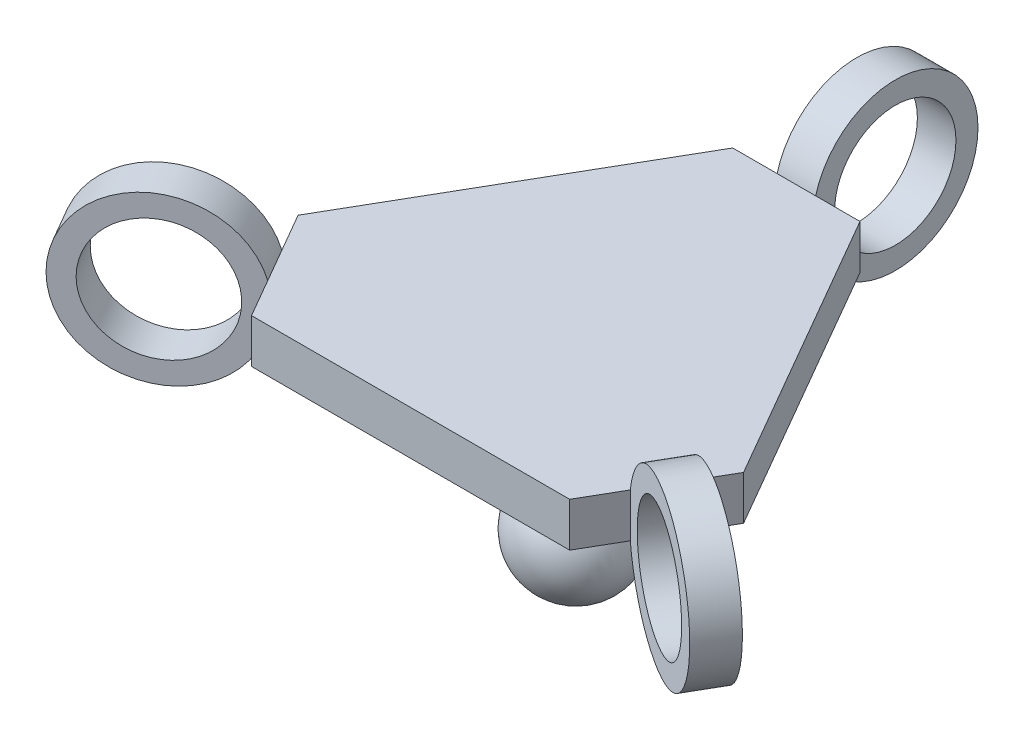
SolidWorks part; units mm, degrees
ref_plane "Front Plane" through (0, 0, 0) normal (0, 0, 1) x (1, 0, 0)
ref_plane "Top Plane" through (0, 0, 0) normal (0, 1, 0) x (1, 0, 0)
ref_plane "Right Plane" through (0, 0, 0) normal (1, 0, 0) x (0, 0, -1)
sketch "Sketch1" plane through (0, 0, 0) normal (0, 1, 0) x (1, 0, 0)
  line L0 (0, 40) -> (0, -30) construction
  line L1 (-11.547, 40) -> (-40.4145, -10)
  line L2 (-28.8675, -30) -> (28.8675, -30)
  line L3 (40.4145, -10) -> (11.547, 40)
  line L4 (11.547, 40) -> (-11.547, 40)
  line L5 (-40.4145, -10) -> (-28.8675, -30)
  line L6 (28.8675, -30) -> (40.4145, -10)
  circle A0 centre (0, 0) radius 30 construction
  circle A1 centre (0, 0) radius 40 construction
  dimension "D2" = 40
  dimension "D1" = 30
  dimension "D3" = 50
extrude "Boss-Extrude1" add sketch "Sketch1" along normal blind 8 contours L4 L1 L5 L2 L6 L3
sketch "Sketch2" plane through (0, 8, 0) normal (0, 1, 0) x (1, 0, 0)
  line L0 (0, 40) -> (0, -30) construction
  line L1 (11.547, 40) -> (-11.547, 40) construction
  line L2 (-28.8675, -30) -> (28.8675, -30) construction
  circle A0 centre (0, 0) radius 5
  dimension "D1" = 10
extrude "Cut-Extrude1" cut sketch "Sketch2" against normal blind 107
sketch "Sketch3" plane through (0, 0, 0) normal (1, 0, 0) x (0, 0, -1)
  line L0 (-34.0107, 3.4198) -> (36.0547, 3.8848) construction
  circle A0 centre (54.4549, 4.0069) radius 15
  dimension "D1" = 30
extrude "Boss-Extrude2" add sketch "Sketch3" along normal blind 3.5 and the other way blind 3.5
sketch "Sketch4" plane through (3.5, 0, 0) normal (1, 0, 0) x (0, 0, -1)
  circle A0 centre (54.4549, 4.0069) radius 11
  dimension "D1" = 22
extrude "Cut-Extrude2" cut sketch "Sketch4" against normal blind 19.5
pattern_circular "CirPattern1" count 3 over 360 about axis through (0, -99, 0) along (0, 1, 0) of bodies 104
sketch "Sketch6" plane through (0, 8, 0) normal (0, 1, 0) x (1, 0, 0)
  circle A0 centre (0, 0) radius 5
extrude "Boss-Extrude3" add sketch "Sketch6" against normal blind 34
sketch "Sketch8" plane through (0, -26, 0) normal (0, -1, 0) x (-1, 0, 0)
  line L0 (0, 0) -> (0, 50000) construction
  line L1 (0, 10) -> (0, -10)
  arc A0 (0, -10) -> (0, 10) centre (0, 0) ccw
  dimension "D1" = 20
revolve "Revolve1" add sketch "Sketch8" angle 360 about L0
